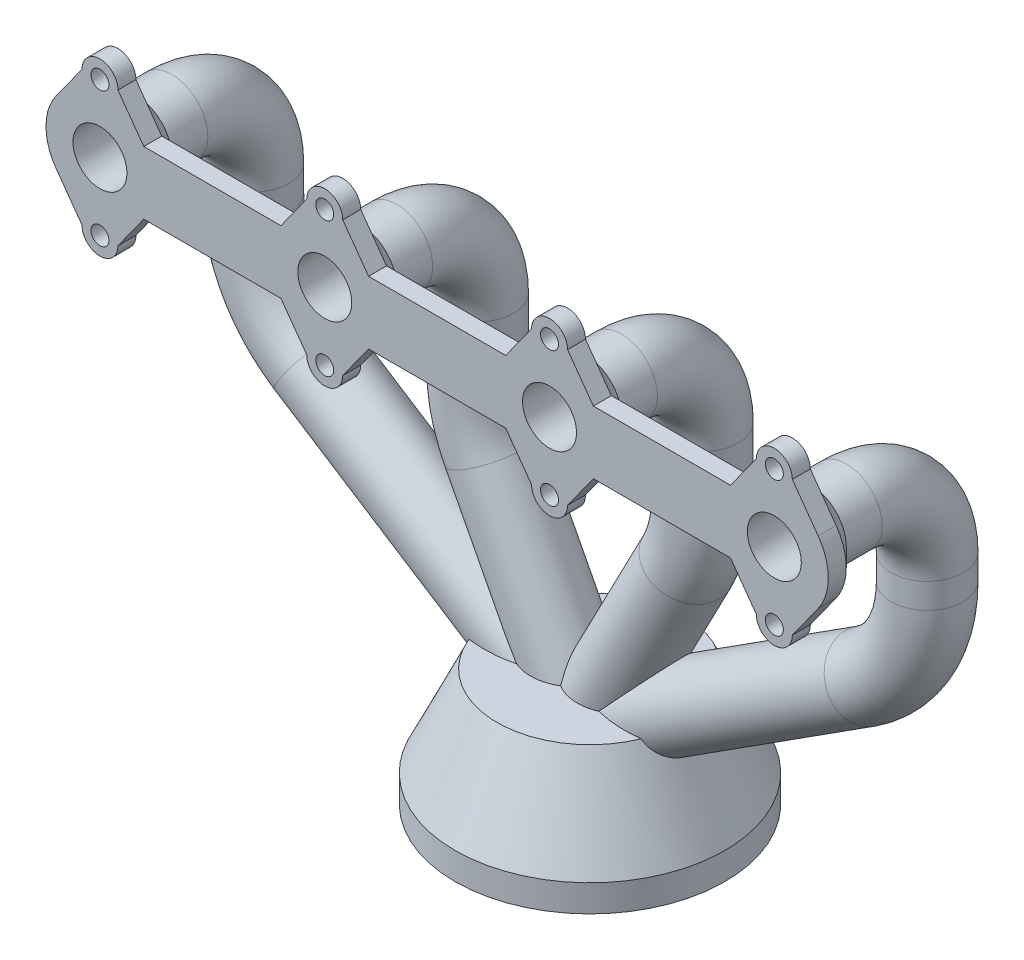
SolidWorks part; units mm, degrees
ref_plane "Front Plane" through (0, 0, 0) normal (0, 0, 1) x (1, 0, 0)
ref_plane "Top Plane" through (0, 0, 0) normal (0, 1, 0) x (1, 0, 0)
ref_plane "Right Plane" through (0, 0, 0) normal (1, 0, 0) x (0, 0, -1)
sketch "Sketch1" plane through (0, 0, 0) normal (0, 0, 1) x (1, 0, 0)
  line L0 (0, 0) -> (43034.3746, 0) construction
  line L1 (0, 0) -> (0, -43034.3746) construction
  line L2 (-75, 0) -> (-75, 15)
  line L3 (-75, 15) -> (-51.6846, 65)
  line L4 (-51.6846, 65) -> (0, 65)
  line L5 (0, 65) -> (0, 0)
  line L6 (0, 0) -> (-75, 0)
  dimension "D1" = 150
  dimension "D2" = 65
  dimension "D3" = 65
  dimension "D4" = 15
revolve "Revolve1" add sketch "Sketch1" angle 360 about L1
ref_plane "Plane1" through (0, 0, 85) normal (0, 0, 1) x (1, 0, 0)
sketch "Sketch2" plane through (0, 0, 85) normal (0, 0, 1) x (1, 0, 0)
  line L0 (0, -4.2644) -> (0, 49995.7356) construction
  line L1 (0, 260) -> (50000, 260) construction
  line L2 (-75, 0) -> (75, 0) construction
  line L3 (-197.5, 297.5) -> (-211.8651, 277.5026)
  line L4 (-177.5, 297.5) -> (-163.1349, 277.5026)
  line L5 (-177.5, 222.5) -> (-163.1349, 242.4974)
  line L6 (-197.5, 222.5) -> (-211.8651, 242.4974)
  line L7 (-72.5, 297.5) -> (-86.8651, 277.5026)
  line L8 (-52.5, 297.5) -> (-38.1349, 277.5026)
  line L9 (-52.5, 222.5) -> (-38.1349, 242.4974)
  line L10 (-72.5, 222.5) -> (-86.8651, 242.4974)
  line L11 (52.5, 297.5) -> (38.1349, 277.5026)
  line L12 (72.5, 297.5) -> (86.8651, 277.5026)
  line L13 (72.5, 222.5) -> (86.8651, 242.4974)
  line L14 (52.5, 222.5) -> (38.1349, 242.4974)
  line L15 (177.5, 297.5) -> (163.1349, 277.5026)
  line L16 (197.5, 297.5) -> (211.8651, 277.5026)
  line L17 (197.5, 222.5) -> (211.8651, 242.4974)
  line L18 (177.5, 222.5) -> (163.1349, 242.4974)
  line L24 (-187.5, 277.4974) -> (187.5, 277.4974)
  line L25 (-187.5, 277.4974) -> (-187.5, 242.4974)
  line L26 (-187.5, 242.4974) -> (187.5, 242.4974)
  line L27 (187.5, 277.4974) -> (187.5, 242.4974)
  arc A0 (-211.8651, 277.5026) -> (-211.8651, 242.4974) centre (-187.5, 260) ccw
  arc A1 (-177.5, 297.5) -> (-197.5, 297.5) centre (-187.5, 297.5) ccw
  arc A3 (-177.5, 222.5) -> (-197.5, 222.5) centre (-187.5, 222.5) cw
  arc A4 (-163.1349, 242.4974) -> (-163.1349, 277.5026) centre (-187.5, 260) ccw
  circle A5 centre (-187.5, 297.5) radius 5
  circle A6 centre (-187.5, 222.5) radius 5
  arc A7 (-86.8651, 277.5026) -> (-86.8651, 242.4974) centre (-62.5, 260) ccw
  arc A8 (-52.5, 297.5) -> (-72.5, 297.5) centre (-62.5, 297.5) ccw
  arc A9 (-52.5, 222.5) -> (-72.5, 222.5) centre (-62.5, 222.5) cw
  arc A10 (-38.1349, 242.4974) -> (-38.1349, 277.5026) centre (-62.5, 260) ccw
  circle A11 centre (-62.5, 297.5) radius 5
  circle A12 centre (-62.5, 222.5) radius 5
  arc A13 (38.1349, 277.5026) -> (38.1349, 242.4974) centre (62.5, 260) ccw
  arc A14 (72.5, 297.5) -> (52.5, 297.5) centre (62.5, 297.5) ccw
  arc A15 (72.5, 222.5) -> (52.5, 222.5) centre (62.5, 222.5) cw
  arc A16 (86.8651, 242.4974) -> (86.8651, 277.5026) centre (62.5, 260) ccw
  circle A17 centre (62.5, 297.5) radius 5
  circle A18 centre (62.5, 222.5) radius 5
  arc A19 (163.1349, 277.5026) -> (163.1349, 242.4974) centre (187.5, 260) ccw
  arc A20 (197.5, 297.5) -> (177.5, 297.5) centre (187.5, 297.5) ccw
  arc A21 (197.5, 222.5) -> (177.5, 222.5) centre (187.5, 222.5) cw
  arc A22 (211.8651, 242.4974) -> (211.8651, 277.5026) centre (187.5, 260) ccw
  circle A23 centre (187.5, 297.5) radius 5
  circle A24 centre (187.5, 222.5) radius 5
  dimension "D3" = 60
  dimension "D4" = 20
  dimension "D5" = 10
  dimension "D1" = 260
  dimension "D2" = 75
  dimension "D6" = 375
  dimension "D8" = 35
  dimension "D7" = 4
extrude "Boss-Extrude1" add sketch "Sketch2" against normal blind 10 separate body contours L17 A22 L16 A20 L15 A19 L24 L27 L26 L18 A21 A23 A24 | L24 A19 L26 L27 | A19 L24 A16 L26 | L26 A16 L24 A13 | L24 A16 L12 A14 L11 A13 A17 | A15 L13 L26 L14 A18 | A13 L24 A10 L26 | L24 A10 L8 A8 L7 A7 A11 | L26 A10 L24 A7 | A9 L9 L26 L10 A12 | A7 L24 A4 L26 | L26 A4 L24 L25 | L24 A4 L4 A1 L3 A0 L6 A3 L5 L26 L25 A5 A6
sketch "Sketch3" plane through (0, 0, 0) normal (1, 0, 0) x (0, 0, -1)
  line L0 (-85, 260) -> (-45, 260)
  line L1 (-85, 277.5026) -> (-85, 242.4974) construction
  line L2 (0, 215) -> (0, 40)
  arc A0 (-45, 260) -> (0, 215) centre (-45, 215) cw
  dimension "D2" = 45
  dimension "D1" = 40
sketch "Sketch4" plane through (0, 0, 0) normal (0, 0, 1) x (1, 0, 0)
  line L0 (187.5, 260) -> (187.5, 201.0449)
  line L1 (152.929, 137.8746) -> (0, 40)
  line L2 (0, 215) -> (0, 40) construction
  line L3 (62.5, 260) -> (62.5, 178.3607)
  line L4 (54.0186, 143.7156) -> (0, 40)
  arc A2 (187.5, 201.0449) -> (152.929, 137.8746) centre (112.5, 201.0449) cw
  arc A3 (62.5, 178.3607) -> (54.0186, 143.7156) centre (-12.5, 178.3607) cw
  point P10 (187.5, 160)
  dimension "D2" = 75
  dimension "D3" = 75
  dimension "D1" = 100
curve "Curve1"
sweep "Sweep1" add path "Curve1" circular profile diameter 40 parameters "D3"=40
mirror "Mirror1" about plane through (0, 0, 0) normal (1, 0, 0) of "Sweep1"
sketch "Sketch10" plane through (0, 0, 0) normal (0, 0, 1) x (1, 0, 0)
  line L0 (0, 0) -> (0, -50000) construction
  line L1 (-65, 0) -> (-65, 12.7831)
  line L2 (-75, 0) -> (75, 0) construction
  line L3 (-65, 12.7831) -> (-45.3139, 55)
  line L4 (-45.3139, 55) -> (0, 55)
  line L5 (0, 55) -> (0, 0)
  line L6 (0, 0) -> (-65, 0)
  line L7 (-75, 15) -> (-75, 0) construction
  line L8 (47.8954, 65) -> (-47.8954, 65) construction
  line L9 (-57.3111, 52.9339) -> (-75, 15) construction
  line L10 (0, 65) -> (-22.8653, 65) construction
  dimension "D1" = 10
  dimension "D2" = 10
  dimension "D3" = 10
revolve "Cut-Revolve1" cut sketch "Sketch10" angle 360 about L0
sweep "Cut-Sweep1" cut path "Curve1" circular profile diameter 30 parameters "D3"=30
mirror "Mirror2" about plane through (0, 0, 0) normal (1, 0, 0) of "Cut-Sweep1"
sketch "Sketch16" plane through (0, 0, 0) normal (0, 1, 0) x (1, 0, 0)
  line L0 (12.5, -85) -> (12.5, -73.951)
  line L1 (-12.5, -85) -> (-12.5, -73.951)
  line L2 (-85, -12.5) -> (-73.951, -12.5)
  line L3 (-85, 12.5) -> (-73.951, 12.5)
  line L4 (-12.5, 85) -> (-12.5, 73.951)
  line L5 (12.5, 85) -> (12.5, 73.951)
  line L6 (85, 12.5) -> (73.951, 12.5)
  line L7 (85, -12.5) -> (73.951, -12.5)
  circle A0 centre (0, 0) radius 85 construction
  arc A1 (-12.4662, -84.0809) -> (12.4662, -84.0809) centre (0, -85) ccw
  circle A2 centre (0, 0) radius 75 construction
  circle A3 centre (0, -85) radius 5
  arc A4 (-84.0809, 12.4662) -> (-84.0809, -12.4662) centre (-85, 0) ccw
  circle A5 centre (-85, 0) radius 5
  arc A6 (12.4662, 84.0809) -> (-12.4662, 84.0809) centre (0, 85) ccw
  circle A7 centre (0, 85) radius 5
  arc A8 (84.0809, -12.4662) -> (84.0809, 12.4662) centre (85, 0) ccw
  circle A9 centre (85, 0) radius 5
  point P9 (0, 0)
  point P10 (0, 0)
  point P13 (0, 0)
  point P40 (0, 0)
  point P41 (0, 0)
  dimension "D1" = 170
  dimension "D2" = 25
  dimension "D3" = 10
  dimension "D4" = 4
extrude "Extrude-Thin1" add sketch "Sketch16" along normal blind 10 separate body thin contours L4 thin type one direction wall 10
chamfer "Chamfer1" distance 10 angle 45 4 edges at (-167.5, 260, 75) (-42.5, 260, 75) (82.5, 260, 75) (207.5, 260, 75)
